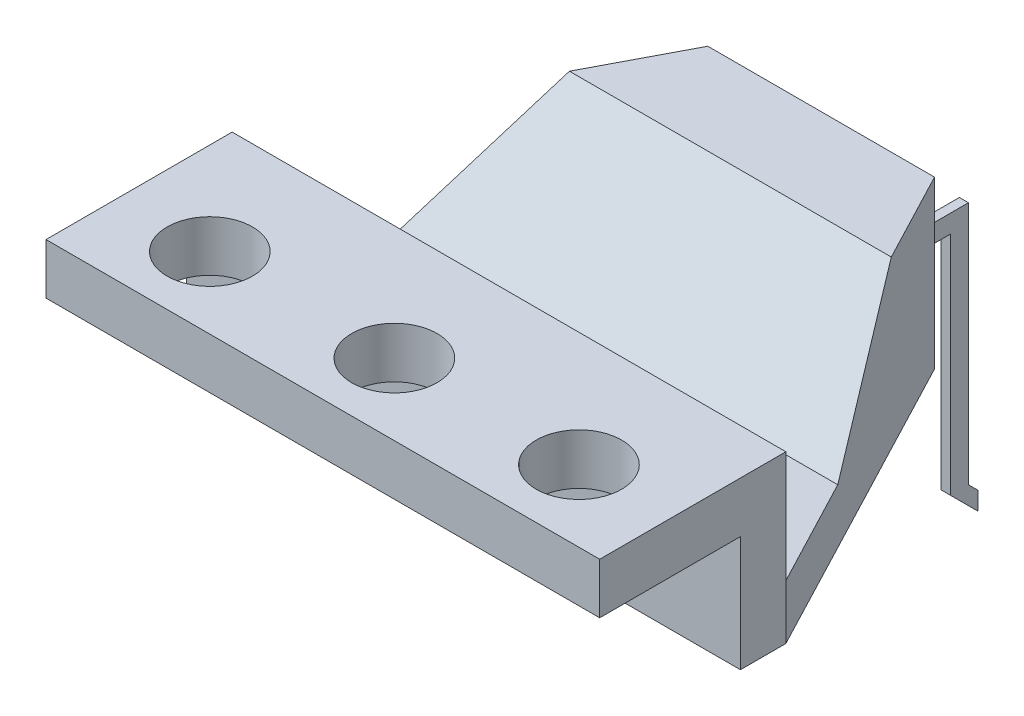
SolidWorks part; units mm, degrees
material "5052-H32"
ref_plane "Front Plane" through (0, 0, 0) normal (0, 0, 1) x (1, 0, 0)
ref_plane "Top Plane" through (0, 0, 0) normal (0, 1, 0) x (1, 0, 0)
ref_plane "Right Plane" through (0, 0, 0) normal (1, 0, 0) x (0, 0, -1)
sketch "Sketch1" plane through (0, 0, 0) normal (1, 0, 0) x (0, 0, -1)
  line L0 (0, 0) -> (0, -2.794)
  line L1 (0, -2.794) -> (7.747, -2.794)
  line L2 (7.747, -2.794) -> (7.747, -9.144)
  line L3 (7.747, -9.144) -> (27.432, -9.144)
  line L4 (27.432, -9.144) -> (27.432, 0)
  line L5 (27.432, 0) -> (22.432, 0)
  line L6 (22.432, 0) -> (16.247, -6.144)
  line L7 (16.247, -6.144) -> (10.247, -6.144)
  line L8 (10.247, -6.144) -> (10.247, 0)
  line L9 (10.247, 0) -> (0, 0)
  line L10 (27.432, -9.144) -> (34.29, -9.144)
  line L11 (34.29, -9.144) -> (34.29, -21.59)
  line L12 (34.29, -21.59) -> (35.814, -23.114)
  line L13 (35.814, -22.114) -> (35.814, -23.114)
  line L14 (35.814, -22.114) -> (35.29, -21.59)
  line L15 (35.29, -21.59) -> (35.29, -8.144)
  line L16 (35.29, -8.144) -> (27.432, -8.144)
  line L17 (34.29, -21.59) -> (35.29, -21.59) construction
  dimension "D1" = 7.747
  dimension "D2" = 2.794
  dimension "D3" = 23.114
  dimension "D4" = 45
  dimension "D5" = 13.97
  dimension "D6" = 1.524
  dimension "D7" = 1
  dimension "D8" = 1
  dimension "D9" = 35.814
  dimension "D10" = 2.5
  dimension "D11" = 3
  dimension "D13" = 6
  dimension "D14" = 5
  dimension "D12" = 8.382
extrude "Boss-Extrude1" add sketch "Sketch1" along normal blind 30.48 contours L8 L9 L0 L1 L2 L3 L4 L5 L6 L7 region at (0, -0.2892, -5.1235)
sketch "Sketch2" plane through (0, 0, 0) normal (0, 1, 0) x (1, 0, 0)
  line L0 (9, 27.432) -> (0, 10.247)
  line L1 (30.48, 27.432) -> (0, 27.432) construction
  line L2 (0, 10.247) -> (0, 0) construction
  line L3 (30.48, 10.247) -> (0, 10.247) construction
  line L4 (21.48, 27.432) -> (30.48, 10.247)
  line L5 (30.48, 0) -> (0, 0) construction
  line L6 (9, 27.432) -> (0, 27.432)
  line L7 (0, 27.432) -> (0, 10.247)
  line L8 (21.48, 27.432) -> (30.48, 27.432)
  line L9 (30.48, 27.432) -> (30.48, 10.247)
  circle A0 centre (5.08, 3.937) radius 2.3495
  circle A1 centre (15.24, 3.937) radius 2.3495
  circle A2 centre (25.4, 3.937) radius 2.3495
  dimension "D5" = 4.699
  dimension "D1" = 5.08
  dimension "D2" = 10.16
  dimension "D3" = 10.16
  dimension "D4" = 3.937
  dimension "D6" = 9
extrude "Cut-Extrude1" cut sketch "Sketch2" against normal blind 10
extrude "Boss-Extrude2" add sketch "Sketch1<4>" along normal blind 0.5 from offset 14.99 contours L17 L12 L13 L14 | L11 L17 L15 L16 L4 L10 region at (0, -8.644, -27.5877) region at (0, -22.1427, -35.2613)
sketch "Sketch1<4>" plane through (0, 0, 0) normal (1, 0, 0) x (0, 0, -1) same geometry as "Sketch1"
sketch "Sketch3" [suppressed] plane through (0, 0, -35.814) normal (0, 0, -1) x (-1, 0, 0)
  line L0 (-15.49, -23.114) -> (-14.99, -23.114) construction
  line L1 (-15.24, -22.114) -> (-15.24, -23.114)
  line L2 (-15.49, -22.114) -> (-14.99, -22.114) construction
  point P0 (-15.24, -23.114)
equation "\"D8@Sketch1\"=\"D7@Sketch1\""
equation "\"D3@Sketch2\"=\"D2@Sketch2\""
